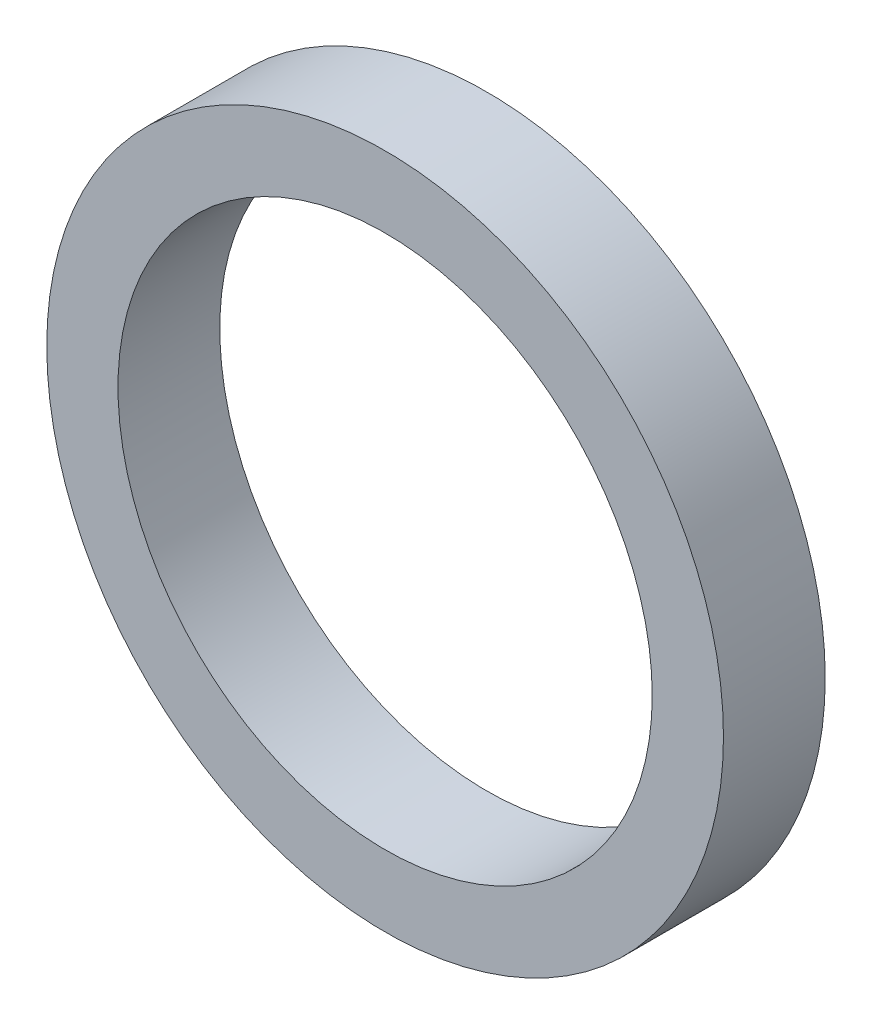
SolidWorks part; units mm, degrees
material "ABS"
ref_plane "Front Plane" through (0, 0, 0) normal (0, 0, 1) x (1, 0, 0)
ref_plane "Top Plane" through (0, 0, 0) normal (0, 1, 0) x (1, 0, 0)
ref_plane "Right Plane" through (0, 0, 0) normal (1, 0, 0) x (0, 0, -1)
sketch "Sketch1" plane through (0, 0, 3) normal (0, 0, 1) x (1, 0, 0)
  circle A0 centre (32.5, 0) radius 2.625
  circle A1 centre (32.5, 0) radius 3.325
  dimension "D1" = 5.25
  dimension "D2" = 6.65
extrude "Boss-Extrude1" add sketch "Sketch1" along normal blind 1
equation "\"RingPinShaft\"= 5.05"
equation "\"CenterBearingOut\"=32.00"
equation "\"OutputBearingOut\"=37.00"
equation "\"RingPostIn\"=5.15"
equation "\"CamBearingOut\"=15.1"
equation "\"DiskOutputShaft\"=10.1"
equation "\"CenterShaft\"=25.2"
equation "\"Eccentricity\"=2"
equation "\"CycCamShaft\"=10.05"
equation "\"m3Thru\"=3.15"
equation "\"m3Insert\"=4.2"
equation "\"D1@Sketch1\"=\"RingPostIn\"+0.1"
equation "\"D2@Sketch1\"=\"RingPostIn\"+1.5"
